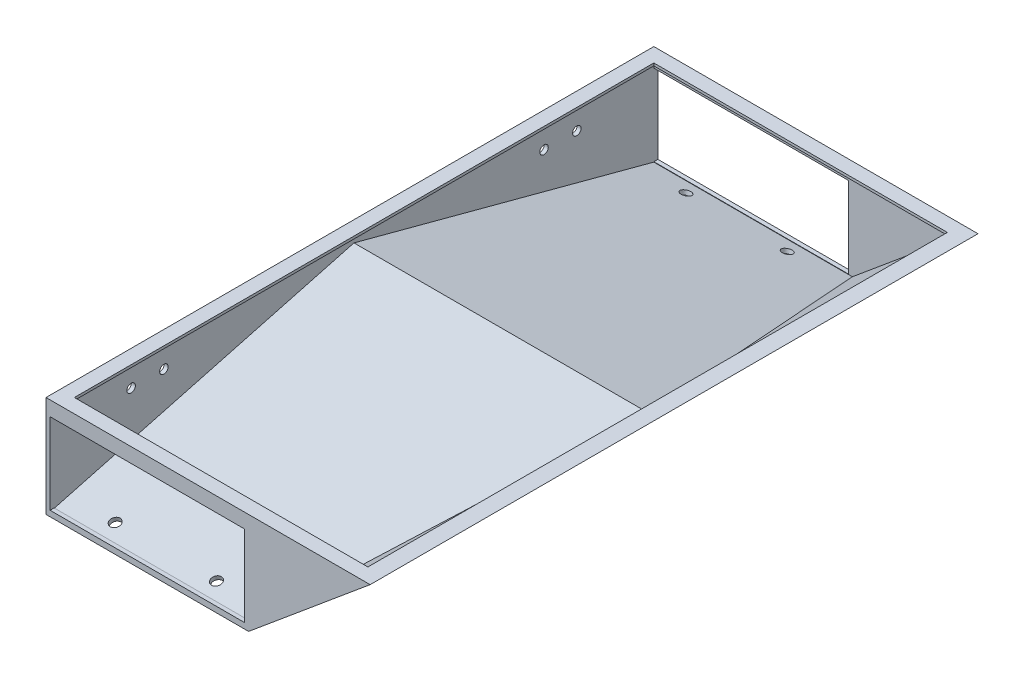
SolidWorks part; units mm, degrees
ref_plane "Front Plane" through (0, 0, 0) normal (0, 0, 1) x (1, 0, 0)
ref_plane "Top Plane" through (0, 0, 0) normal (0, 1, 0) x (1, 0, 0)
ref_plane "Right Plane" through (0, 0, 0) normal (1, 0, 0) x (0, 0, -1)
sketch "Sketch2" plane through (0, 0, 0) normal (0, 0, 1) x (1, 0, 0)
  line L0 (0, 0) -> (127, 0)
  line L1 (127, 0) -> (203.2, 63.5)
  line L3 (203.2, 63.5) -> (0, 63.5)
  line L4 (0, 63.5) -> (0, 0)
  dimension "D1" = 203.2
  dimension "D3" = 63.5
  dimension "D4" = 76.2
extrude "Boss-Extrude1" add sketch "Sketch2" along normal blind 381
sketch "Sketch3" plane through (0, 0, 0) normal (-1, 0, 0) x (0, 0, 1)
  line L0 (190.5, 0) -> (190.5, 63.5) construction
  line L1 (381, 0) -> (0, 0) construction
  line L2 (381, 63.5) -> (0, 63.5) construction
  line L6 (0, 0) -> (381, 0)
  line L7 (381, 0) -> (190.5, 50.8)
  line L8 (190.5, 50.8) -> (0, 0)
  dimension "D1" = 50.8
extrude "Cut-Extrude1" cut sketch "Sketch3" against normal blind 304.8
sketch "Sketch4" plane through (0, 0, 381) normal (0, 0, 1) x (1, 0, 0)
  line L2 (0, 63.5) -> (0, 0) construction
  line L5 (2.54, 3.556) -> (124.46, 3.556)
  line L6 (2.54, 3.556) -> (2.54, 54.356)
  line L9 (2.54, 54.356) -> (124.46, 54.356)
  line L10 (124.46, 3.556) -> (124.46, 54.356)
  line L11 (0, 0) -> (127, 0) construction
  dimension "D2" = 3.556
  dimension "D3" = 121.92
  dimension "D1" = 2.54
  dimension "D4" = 50.8
shell "Shell1" thickness 2.54 removed face at (101.6, 63.5, 190.5)
extrude "Cut-Extrude3" cut sketch "Sketch4" against normal blind 2.54
extrude "Cut-Extrude4" cut sketch "Sketch4<4>" along normal blind 2.54 from surface starting at face at (82.55, 31.75, 0)
sketch "Sketch4<4>" plane through (0, 0, 381) normal (0, 0, 1) x (1, 0, 0) same geometry as "Sketch4"
sketch "Sketch5" plane through (0, 94.8548, 25.2946) normal (0, -0.9662, -0.2577) x (1, 0, 0)
  line L0 (0, 355.4355) -> (130.9268, 355.4355) construction
  line L1 (0, 368.1355) -> (0, 170.9785) construction
  line L2 (127, 368.1355) -> (187.96, 170.9785) construction
  line L3 (0, 368.1355) -> (127, 368.1355) construction
  circle A0 centre (31.75, 355.4355) radius 3.175
  circle A1 centre (95.25, 355.4355) radius 3.175
  dimension "D2" = 6.35
  dimension "D3" = 31.75
  dimension "D4" = 63.5
  dimension "D1" = 12.7
extrude "Cut-Extrude5" cut sketch "Sketch5" against normal blind 2.54
ref_plane "Plane1" through (0, 0, 190.5) normal (0, 0, 1) x (1, 0, 0)
mirror "Mirror1" about plane through (0, 0, 190.5) normal (0, 0, 1) of "Cut-Extrude5"
sketch "Sketch7" plane through (0, 0, 0) normal (0, 1, 0) x (1, 0, 0)
  line L6 (2.54, -2.54) -> (199.2324, -2.54)
  line L7 (2.54, -2.54) -> (2.54, -378.46)
  line L8 (2.54, -378.46) -> (199.2324, -378.46)
  line L9 (199.2324, -2.54) -> (199.2324, -378.46)
  line L35 (8.89, -372.11) -> (126.9997, -372.11)
  line L36 (126.9997, -372.11) -> (192.8824, -372.11)
  line L37 (8.89, -190.5) -> (8.89, -372.11)
  line L38 (8.89, -8.89) -> (8.89, -190.5)
  line L39 (192.8824, -372.11) -> (192.8824, -8.89)
  line L40 (192.8824, -8.89) -> (126.9997, -8.89)
  line L41 (126.9997, -8.89) -> (8.89, -8.89)
  line L42 (8.89, -372.11) -> (126.9997, -372.11)
  line L43 (126.9997, -372.11) -> (192.8824, -372.11)
  line L44 (8.89, -190.5) -> (8.89, -372.11)
  line L45 (8.89, -8.89) -> (8.89, -190.5)
  line L46 (192.8824, -372.11) -> (192.8824, -8.89)
  line L47 (192.8824, -8.89) -> (126.9997, -8.89)
  line L48 (126.9997, -8.89) -> (8.89, -8.89)
  dimension "D1" = 6.35
extrude "Boss-Extrude2" add sketch "Sketch7" against normal blind 1.5875 from surface starting at face at (101.6, 63.5, 190.5)
sketch "Sketch8" plane through (0, 0, 0) normal (-1, 0, 0) x (0, 0, 1)
  line L0 (381, 63.5) -> (0, 63.5) construction
  line L1 (381, 63.5) -> (381, 0) construction
  circle A0 centre (309.626, 44.45) radius 2.667
  circle A1 centre (330.2, 44.45) radius 2.667
  dimension "D2" = 5.334
  dimension "D3" = 19.05
  dimension "D1" = 20.574
  dimension "2" = 50.8
extrude "Cut-Extrude6" cut sketch "Sketch8" against normal blind 2.54
mirror "Mirror2" about plane through (0, 0, 190.5) normal (0, 0, 1) of "Cut-Extrude6"
